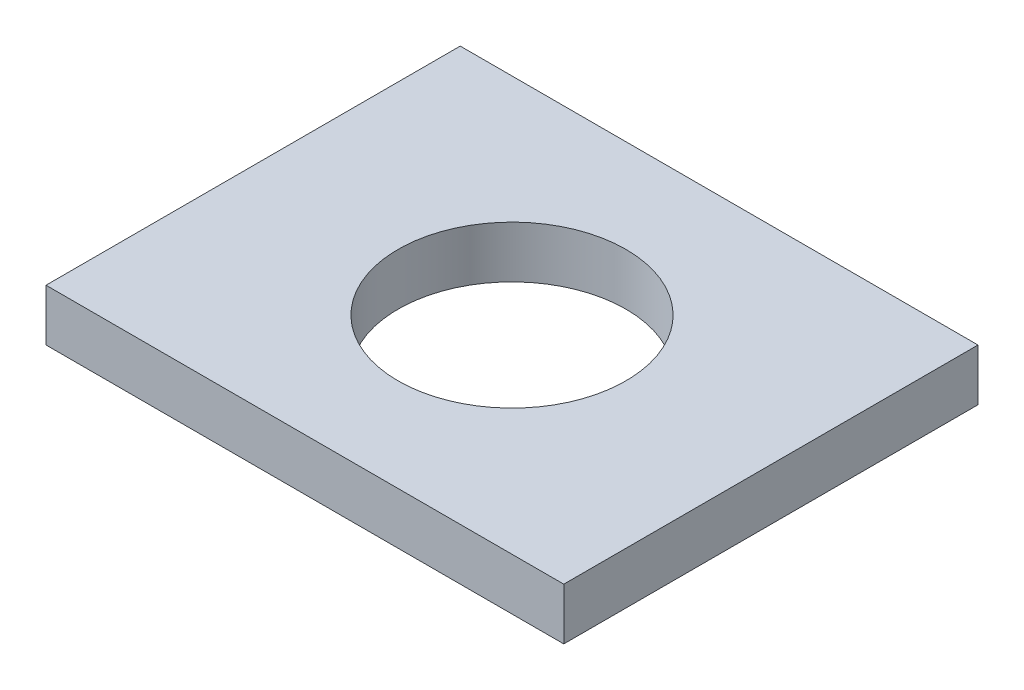
SolidWorks part; units mm, degrees
ref_plane "Front Plane" through (0, 0, 0) normal (0, 0, 1) x (1, 0, 0)
ref_plane "Top Plane" through (0, 0, 0) normal (0, 1, 0) x (1, 0, 0)
ref_plane "Right Plane" through (0, 0, 0) normal (1, 0, 0) x (0, 0, -1)
sketch "Sketch1" plane through (0, 0, 0) normal (0, 1, 0) x (1, 0, 0)
  line L1 (-25, 20) -> (25, 20)
  line L2 (-25, 20) -> (-25, -20)
  line L3 (-25, -20) -> (25, -20)
  line L4 (25, 20) -> (25, -20)
  line L5 (-25, 20) -> (25, -20) construction
  line L6 (-25, -20) -> (25, 20) construction
  point P0 (0, 0)
  dimension "D1" = 50
  dimension "D2" = 40
extrude "Boss-Extrude1" add sketch "Sketch1" along normal blind 5
sketch "Sketch2" plane through (0, 5, 0) normal (0, 1, 0) x (1, 0, 0)
  circle A0 centre (0, 0) radius 11
  dimension "D1" = 22
extrude "Cut-Extrude1" cut sketch "Sketch2" against normal through all
